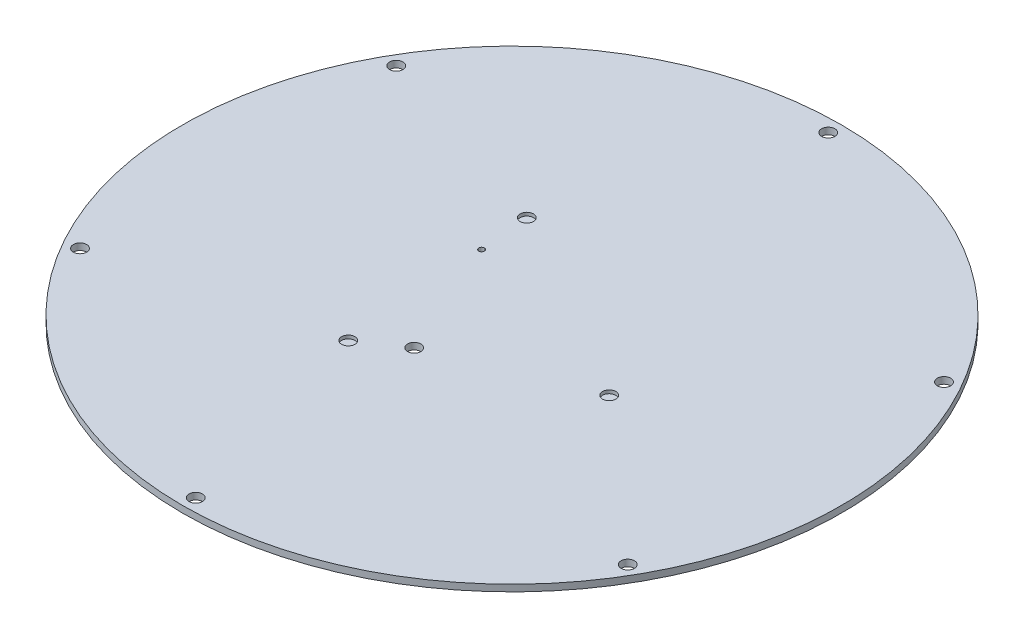
SolidWorks part; units mm, degrees
material "1060 Alloy"
ref_plane "Front Plane" through (0, 0, 0) normal (0, 0, 1) x (1, 0, 0)
ref_plane "Top Plane" through (0, 0, 0) normal (0, 1, 0) x (1, 0, 0)
ref_plane "Right Plane" through (0, 0, 0) normal (1, 0, 0) x (0, 0, -1)
sketch "Sketch1" plane through (0, 0, 0) normal (0, 1, 0) x (1, 0, 0)
  circle A0 centre (0, 0) radius 49.5
  circle A1 centre (0, 47.5) radius 1
  circle A2 centre (41.1362, 23.75) radius 1
  circle A3 centre (41.1362, -23.75) radius 1
  circle A4 centre (0, -47.5) radius 1
  circle A5 centre (-41.1362, -23.75) radius 1
  circle A6 centre (-41.1362, 23.75) radius 1
  point P17 (0, 0)
  dimension "D1" = 99
  dimension "D2" = 2
  dimension "D3" = 47.5
  dimension "D4" = 6
extrude "Boss-Extrude1" add sketch "Sketch1" along normal blind 1
sketch "Sketch2" plane through (0, 1, 0) normal (0, 1, 0) x (1, 0, 0)
  line L0 (12.1829, 21.1013) -> (0, 0) construction
  line L1 (0, 0) -> (-13.509, -23.3983) construction
  line L2 (0, 0) -> (-7.5117, -28.0339) construction
  line L3 (0, 0) -> (0, -23.2906) construction
  line L4 (0, -23.2906) -> (0, 0) construction
  line L5 (0, 0) -> (-12.9568, 7.4806) construction
  circle A1 centre (-3.1058, -11.5911) radius 1
  circle A2 centre (-10.8253, 6.25) radius 0.42
  dimension "D1" = 0.84
  dimension "D3" = 2
  dimension "D2" = 12.5
  dimension "D4" = 12
  dimension "D5" = 15
  dimension "D6" = 30
  dimension "D7" = 90
  dimension "D8" = 0
extrude "Cut-Extrude1" cut sketch "Sketch2" against normal through all both and the other way through all
sketch "Sketch3" plane through (0, 1, 0) normal (0, 1, 0) x (1, 0, 0)
  line L0 (17.7265, -3.1257) -> (0, 0) construction
  line L1 (0, 0) -> (-11.5702, 13.7888) construction
  line L2 (-11.5702, 13.7888) -> (0, 0) construction
  line L3 (0, 0) -> (-9, -15.5885) construction
  line L4 (-9, -15.5885) -> (0, 0) construction
  line L5 (0, 0) -> (41.1362, -23.75) construction
  circle A0 centre (0, 0) radius 18
  circle A1 centre (-9, -15.5885) radius 1
  circle A2 centre (17.7265, -3.1257) radius 1
  circle A3 centre (-11.5702, 13.7888) radius 1
  dimension "D1" = 36
  dimension "D2" = 2
  dimension "D3" = 2
  dimension "D4" = 2
  dimension "D5" = 90
  dimension "D6" = 110
  dimension "D7" = 140
extrude "Cut-Extrude2" cut sketch "Sketch3" against normal blind 0.5 contours A0 A2 | A0 A2 | A0 A1 | A0 A1 | A0 A3 | A0 A3 region at (-11.2942, 1, -13.4599) region at (-11.8397, 1, -14.1101) region at (18.1395, 1, 3.1985) region at (17.3037, 1, 3.0511) region at (-8.7853, 1, 15.2166) region at (-9.2097, 1, 15.9516)
